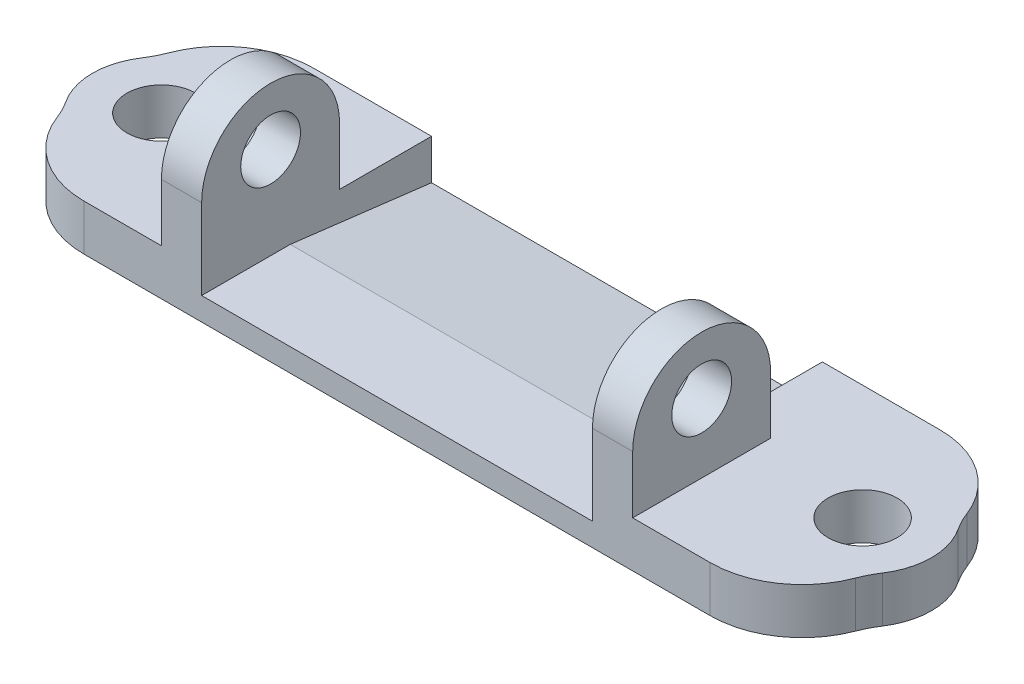
SolidWorks part; units mm, degrees
note: '?' marks a value the reader was unsure of.
ref_plane "Front Plane" through (0, 0, 0) normal (0, 0, 1) x (1, 0, 0)
ref_plane "Top Plane" through (0, 0, 0) normal (0, 1, 0) x (1, 0, 0)
ref_plane "Right Plane" through (0, 0, 0) normal (1, 0, 0) x (0, 0, -1)
ref_plane "Plane1" through (0, 4, 0) normal (0, 1, 0) x (1, 0, 0)
sketch "Sketch1" plane through (0, 4, 0) normal (0, 1, 0) x (1, 0, 0)
  line L0 (7.754, 0) -> (62.246, 0)
  line L1 (62.246, 20) -> (52, 20)
  line L2 (18, 20) -> (7.754, 20)
  arc A0 (62.246, 0) -> (69.7238, 5.1571) centre (62.246, 8) ccw
  arc A1 (69.7238, 5.1571) -> (70.515, 6.7061) centre (77.2017, 2.3142) cw
  arc A2 (70.515, 6.7061) -> (70.515, 13.2939) centre (65.5, 10) ccw
  arc A3 (70.515, 13.2939) -> (69.7238, 14.8429) centre (77.2017, 17.6858) cw
  arc A4 (69.7238, 14.8429) -> (62.246, 20) centre (62.246, 12) ccw
  arc A5 (7.754, 20) -> (0.2762, 14.8429) centre (7.754, 12) ccw
  arc A6 (0.2762, 14.8429) -> (-0.515, 13.2939) centre (-7.2017, 17.6858) cw
  arc A7 (-0.515, 13.2939) -> (-0.515, 6.7061) centre (4.5, 10) ccw
  arc A8 (-0.515, 6.7061) -> (0.2762, 5.1571) centre (-7.2017, 2.3142) cw
  arc A9 (0.2762, 5.1571) -> (7.754, 0) centre (7.754, 8) ccw
  spline S0 degree 3 poles (18, 20) (29.3333, 20) (40.6667, 20) (52, 20) knots 0 0 0 0 1 1 1 1
extrude "Boss-Extrude1" add sketch "Sketch1" against normal blind 4
ref_plane "Plane2" through (18, 0, 0) normal (-1, 0, 0) x (0, -1, 0)
sketch "Sketch2" plane through (18, 0, 0) normal (-1, 0, 0) x (0, -1, 0)
  line L0 (-2, 0) -> (-4, 0)
  line L1 (-4, 0) -> (-4, -20)
  line L2 (-4, -20) -> (-0.4994, -20)
  line L3 (-0.4994, -20) -> (-2, -7.7072)
  line L4 (-2, -7.7072) -> (-2, 0)
extrude "Cut-Extrude1" cut sketch "Sketch2" against normal blind 34
ref_plane "Plane3" through (18, 0, 0) normal (1, 0, 0) x (0, 0, -1)
sketch "Sketch3" plane through (18, 0, 0) normal (1, 0, 0) x (0, 0, -1)
  line L0 (0, 4) -> (12, 4)
  line L1 (12, 4) -> (12, 9)
  line L2 (0, 9) -> (0, 4)
  arc A0 (12, 9) -> (0, 9) centre (6, 9) ccw
extrude "Boss-Extrude2" add sketch "Sketch3" against normal blind 3.5
ref_plane "Plane4" through (35, 0, 0) normal (-1, 0, 0) x (0, 0, 1)
mirror "Mirror1" about plane through (35, 0, 0) normal (-1, 0, 0) of "Boss-Extrude2"
hole_wizard "Ø5.2 (5.2) Diameter Hole1" positions "Sketch8" profile "Sketch7" hole size "Ø5.2" standard "ANSI Metric"
sketch "Sketch8" plane through (14.5, 0, 0) normal (-1, 0, 0) x (0, 0, 1)
  point P0 (-6, 10)
sketch "Sketch7" plane through (14.5, 10, -6) normal (0, 1, 0) x (0, 0, 1)
  line L0 (0, 0) -> (0, 41)
  line L1 (0, 41) -> (2.6, 41)
  line L2 (2.6, 41) -> (2.6, 0)
  line L5 (2.6, 0) -> (0, 0)
  line L11 (0, -6.35) -> (0, 107.95) construction
  dimension "Thru Hole Dia." = 5.2
  dimension "Thru Hole Depth" = 41
hole_wizard "Ø6.0 (6) Diameter Hole1" positions "Sketch10" profile "Sketch9" hole size "Ø6.0" standard "ANSI Metric"
sketch "Sketch10" plane through (0, 0, 0) normal (0, -1, 0) x (-1, 0, 0)
  point P0 (-4.5, 10)
sketch "Sketch9" plane through (4.5, 0, -10) normal (1, 0, 0) x (0, 0, -1)
  line L0 (0, 0) -> (0, 15)
  line L1 (0, 15) -> (3, 15)
  line L2 (3, 15) -> (3, 0)
  line L5 (3, 0) -> (0, 0)
  line L11 (0, -6.35) -> (0, 107.95) construction
  dimension "Thru Hole Dia." = 6
  dimension "Thru Hole Depth" = 15
mirror "Mirror2" about plane through (35, 0, 0) normal (-1, 0, 0) of "Ø6.0 (6) Diameter Hole1", "Ø5.2 (5.2) Diameter Hole1"
ref_axis "Axis1" through (12.0079, 10, -6) along (1, 0, 0)?
ref_axis "Axis2" through (65.5, 4, -10) along (0, -1, 0)?
ref_axis "Axis3" through (4.5, 4, -10) along (0, -1, 0)?
ref_plane "Plane5" through (35, 0, 0) normal (1, 0, 0) x (0, 0, -1)
